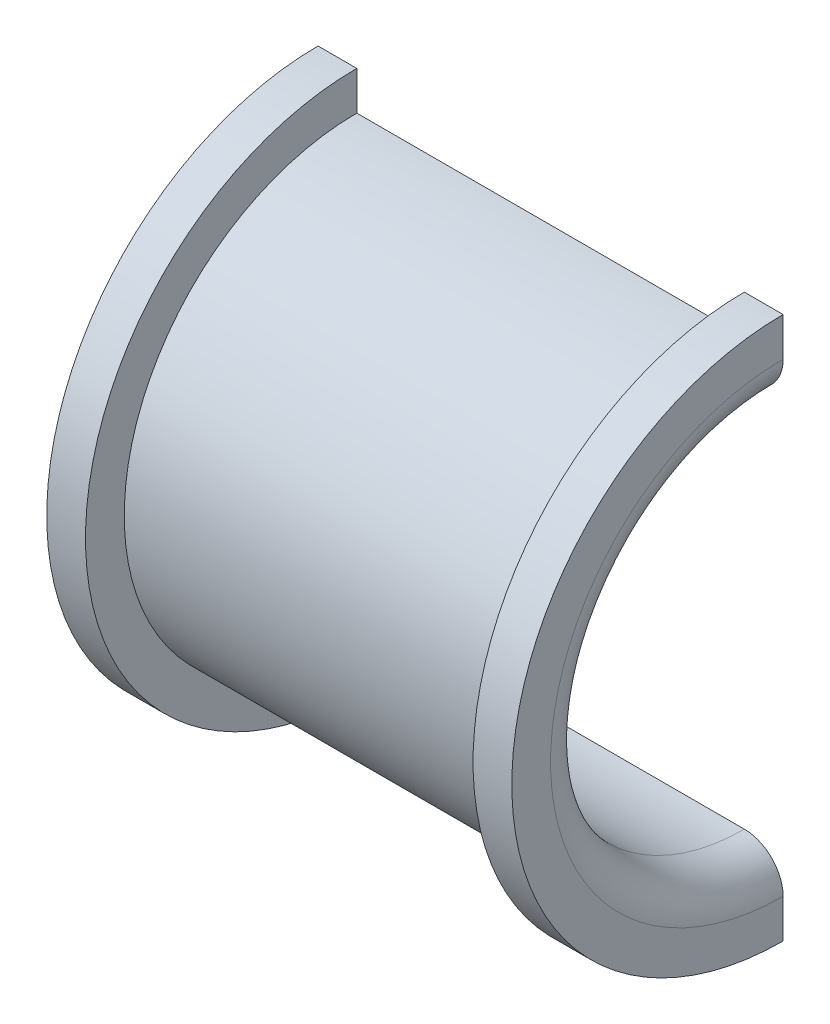
SolidWorks part; units mm, degrees
material "Brass"
ref_plane "Front Plane" through (0, 0, 0) normal (0, 0, 1) x (1, 0, 0)
ref_plane "Top Plane" through (0, 0, 0) normal (0, 1, 0) x (1, 0, 0)
ref_plane "Right Plane" through (0, 0, 0) normal (1, 0, 0) x (0, 0, -1)
sketch "Sketch1" plane through (0, 0, 0) normal (1, 0, 0) x (0, 0, -1)
  circle A0 centre (0, 0) radius 25
  circle A1 centre (0, 0) radius 30
  dimension "D1" = 50
  dimension "D2" = 60
extrude "Boss-Extrude1" add sketch "Sketch1" along normal mid plane 50
sketch "Sketch2" plane through (25, 0, 0) normal (1, 0, 0) x (0, 0, -1)
  circle A0 centre (0, 0) radius 35
  circle A1 centre (0, 0) radius 25 construction
  circle A2 centre (0, 0) radius 25
  dimension "D1" = 70
extrude "Boss-Extrude2" add sketch "Sketch2" along normal blind 5
mirror "Mirror3" about plane through (0, 0, 0) normal (1, 0, 0) of "Boss-Extrude2"
fillet "Fillet1" radius 5 2 edges at (-30, 0, -25) (30, 0, -25)
sketch "Sketch3" plane through (30, 0, 0) normal (1, 0, 0) x (0, 0, -1)
  line L1 (0, -51.4182) -> (61.0257, -51.4182)
  line L2 (0, -51.4182) -> (0, 56.8056)
  line L3 (0, 56.8056) -> (61.0257, 56.8056)
  line L4 (61.0257, -51.4182) -> (61.0257, 56.8056)
extrude "Cut-Extrude1" cut sketch "Sketch3" against normal through all both and the other way through all
